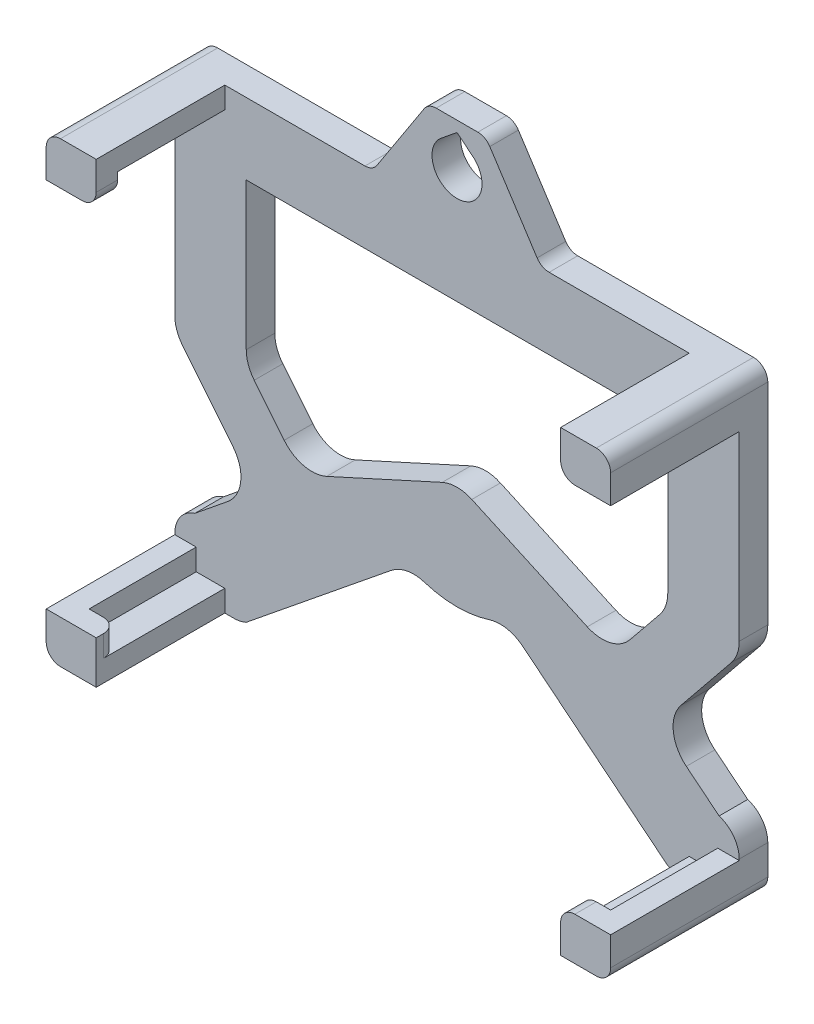
SolidWorks part; units mm, degrees
ref_plane "Front Plane" through (0, 0, 0) normal (0, 0, 1) x (1, 0, 0)
ref_plane "Top Plane" through (0, 0, 0) normal (0, 1, 0) x (1, 0, 0)
ref_plane "Right Plane" through (0, 0, 0) normal (1, 0, 0) x (0, 0, -1)
sketch "Sketch1" plane through (0, 0, 0) normal (0, 0, 1) x (1, 0, 0)
  line L4 (-3, -3) -> (76, -3)
  line L5 (76, -3) -> (76, 61)
  line L6 (76, 61) -> (-3, 61)
  line L7 (-3, 61) -> (-3, -3)
  line L8 (-3, -3) -> (-3, 7.5757)
extrude "Boss-Extrude1" add sketch "Sketch1" along normal blind 4 contours L6 L7 L4 L5 region at (36.5, 29, 0)
sketch "Sketch2" plane through (0, 0, 4) normal (0, 0, 1) x (1, 0, 0)
  line L2 (4, 61) -> (4.1974, 61.1407)
  line L3 (4, 58) -> (4, 61)
  line L4 (-3, -3) -> (-3, 3)
  line L6 (-3, -3) -> (4, -3)
  line L8 (-3, 3) -> (0, 3)
  line L9 (0, 3) -> (0, 0)
  line L10 (0, 0) -> (4, 0)
  line L11 (4, 0) -> (4, -3)
  line L12 (4, -3) -> (4.1974, -3.1407)
  line L13 (0, 58) -> (4, 58)
  line L14 (0, 55) -> (0, 58)
  line L15 (-3, 55) -> (0, 55)
  line L16 (-3, 61) -> (4, 61)
  line L17 (-3, 61) -> (-3, 55)
  line L18 (76, 61) -> (76, 55)
  line L19 (76, 61) -> (69, 61)
  line L20 (76, 55) -> (73, 55)
  line L21 (73, 55) -> (73, 58)
  line L22 (73, 58) -> (69, 58)
  line L23 (69, -3) -> (68.8026, -3.1407)
  line L24 (69, 0) -> (69, -3)
  line L25 (73, 0) -> (69, 0)
  line L26 (73, 3) -> (73, 0)
  line L27 (76, 3) -> (73, 3)
  line L28 (76, -3) -> (69, -3)
  line L29 (76, -3) -> (76, 3)
  line L30 (69, 58) -> (69, 61)
  line L31 (69, 61) -> (68.8026, 61.1407)
  point P3 (0, 0)
  line M8 (76, 61) -> (-3, 61)
  line M9 (-3, 61) -> (-3, -3)
  line M10 (-3, -3) -> (76, -3)
  line M11 (76, -3) -> (76, 61)
extrude "Boss-Extrude2" add sketch "Sketch2" along normal blind 15 contours L27 L26 L25 L24 M11 M10 | L11 L10 L9 L8 M9 M10 | L15 L14 L13 L3 M9 M8 | L30 L22 L21 L20 M11 M8 region at (-0.1, 58.6, 4) region at (73.1, 58.6, 4) region at (-0.1, -0.6, 4) region at (73.1, -0.6, 4)
sketch "Sketch3" plane through (0, 0, 19) normal (0, 0, 1) x (1, 0, 0)
  line L1 (-3, 61) -> (4, 61)
  line L2 (-3, 61) -> (-3, 55)
  line L3 (-3, 55) -> (4, 55)
  line L4 (4, 61) -> (4, 55)
  line L9 (4, -3) -> (4, 3)
  line L10 (-3, 3) -> (4, 3)
  line L11 (-3, -3) -> (-3, 3)
  line L12 (-3, -3) -> (4, -3)
  line L13 (76, -3) -> (69, -3)
  line L14 (76, -3) -> (76, 3)
  line L15 (76, 3) -> (69, 3)
  line L16 (69, -3) -> (69, 3)
  line L17 (69, 61) -> (69, 55)
  line L18 (76, 55) -> (69, 55)
  line L19 (76, 61) -> (76, 55)
  line L20 (76, 61) -> (69, 61)
extrude "Boss-Extrude3" add sketch "Sketch3" along normal blind 3
sketch "Sketch4" plane through (0, 0, 0) normal (0, 0, -1) x (-1, 0, 0)
  line L0 (-66, 51) -> (-7, 51)
  line L1 (3, -3) -> (-76, -3) construction
  line L2 (-66, -3) -> (-66, -2.6206)
  line L3 (-73.1879, 7) -> (-76, 7)
  line L4 (-76, -3) -> (-76, 61) construction
  line L5 (-76, 27.8038) -> (-76, 7)
  line L6 (-58.2557, 19.0969) -> (-73.1879, 7)
  line L7 (-29.5947, 15.684) -> (-7, -2.6206)
  line L8 (3, 27.8038) -> (3, 7)
  line L9 (0.1879, 7) -> (3, 7)
  line L10 (-7, -3) -> (-7, -2.6206)
  line L11 (-58.2557, 19.0969) -> (-36.5, 29)
  line L12 (-66, 28.6562) -> (-58.2557, 19.0969)
  line L13 (-14.7443, 19.0969) -> (0.1879, 7)
  line L14 (-36.5, 29) -> (-14.7443, 19.0969)
  line L15 (-43.4053, 15.684) -> (-66, -2.6206)
  line L16 (-36.5, 61) -> (-36.5, 63.2092)
  line L17 (-66, -3) -> (-7, -3)
  line L19 (-76, 61) -> (3, 61) construction
  line L22 (-76, 27.8038) -> (-64.7102, 13.868)
  line L23 (-66, 51) -> (-66, 28.6562)
  line L25 (3, 27.8038) -> (-8.2898, 13.868)
  line L26 (-7, 28.6562) -> (-14.7443, 19.0969)
  line L27 (-7, 51) -> (-7, 28.6562)
  arc A0 (-43.4053, 15.684) -> (-29.5947, 15.684) centre (-36.5, 29) ccw
  line M11 (-76, 61) -> (-76, -3)
  line M12 (-76, -3) -> (3, -3)
  line M13 (3, -3) -> (3, 61)
extrude "Cut-Extrude1" cut sketch "Sketch4" against normal blind 4 contours L3 L6 M11 | A0 L15 L2 L10 L7 M12 | L25 L13 L9 M13 | L27 L0 L23 L12 L11 L14 L26 region at (36.5, 37.3529, 0) region at (72.1655, 15.697, 0) region at (0.8345, 15.697, 0) region at (36.5, 4.1489, 0)
sketch "Sketch5" plane through (0, 0, 0) normal (0, 0, -1) x (-1, 0, 0)
  line L1 (-76, 61) -> (3, 61) construction
  line L2 (-32.5, 73) -> (-40.5, 73)
  line L3 (-40.5, 73) -> (-48.3029, 61)
  line L4 (-32.5, 73) -> (-24.6971, 61)
  line L6 (-36.5, 71.5) -> (-38.8266, 69.6147)
  line L7 (-36.5, 71.5) -> (-34.1734, 69.6147)
  arc A0 (-38.8266, 69.6147) -> (-34.1734, 69.6147) centre (-36.5, 67) ccw
  line M10 (3, 61) -> (-76, 61)
extrude "Boss-Extrude4" add sketch "Sketch5" against normal blind 4 contours L4 L2 L3 A0 L6 L7 M10 region at (28.8206, 66.8556, 0)
fillet "Fillet1" radius 2 12 edges at (24.6971, 61, 2) (48.3029, 61, 2) (40.5, 73, 2) (32.5, 73, 2) (4, 55, 20.5) (69, 55, 20.5) (69, 3, 20.5) (4, 1.5, 19) (-3, -3, 11) (76, -3, 11) (76, 61, 11) (-3, 61, 11)
fillet "Fillet2" radius 5 11 edges at (8.2898, 13.868, 2) (-3, 27.8038, 2) (76, 27.8038, 2) (64.7102, 13.868, 2) (43.4053, 15.684, 2) (29.5947, 15.684, 2) (7, 28.6562, 2) (66, 28.6562, 2) (58.2557, 19.0969, 2) (14.7443, 19.0969, 2) (36.5, 29, 2)
fillet "Fillet3" radius 4 4 edges at (76, 7, 2) (-3, 7, 2) (66, -3, 2) (7, -3, 2)
